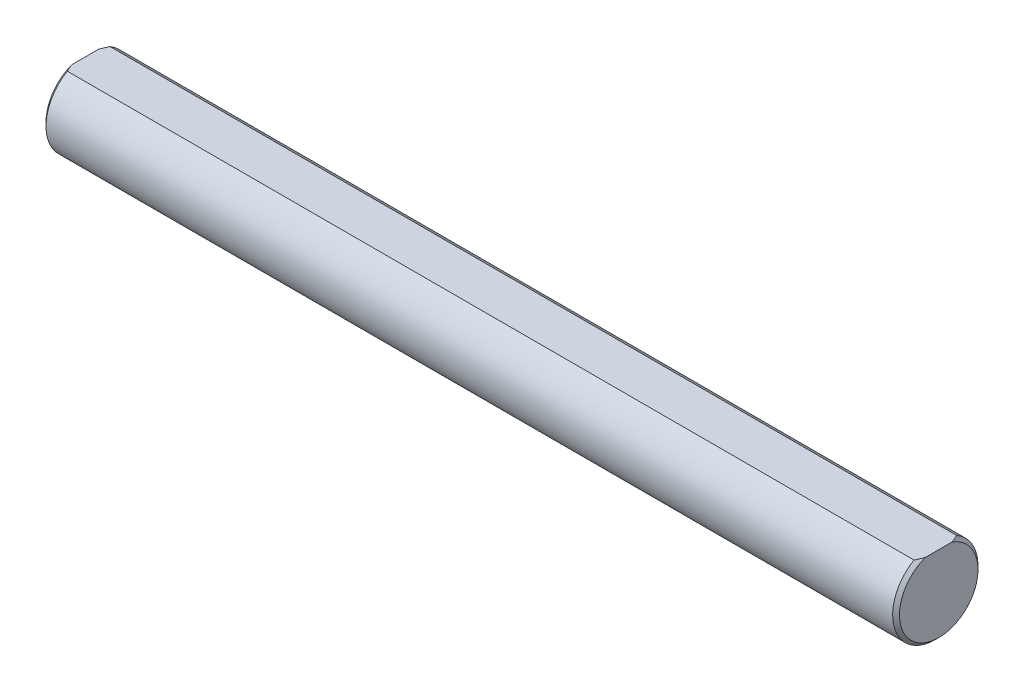
SolidWorks part; units mm, degrees
material "AISI 1045 Steel, cold drawn"
ref_plane "Front Plane" through (0, 0, 0) normal (0, 0, 1) x (1, 0, 0)
ref_plane "Top Plane" through (0, 0, 0) normal (0, 1, 0) x (1, 0, 0)
ref_plane "Right Plane" through (0, 0, 0) normal (1, 0, 0) x (0, 0, -1)
sketch "Sketch1" plane through (0, 0, 0) normal (1, 0, 0) x (0, 0, -1)
  circle A2 centre (0, 0) radius 3.175
  dimension "D1" = 6.35
extrude "Boss-Extrude1" add sketch "Sketch1" along normal blind 63.5
chamfer "Chamfer1" distance 0.254 angle 45 2 edges at (63.5, 0, -3.175) (0, 0, -3.175)
sketch "Sketch2" plane through (63.5, 0, 0) normal (1, 0, 0) x (0, 0, -1)
  line L0 (-1.5875, 2.7496) -> (1.5875, 2.7496)
  circle A0 centre (0, 0) radius 3.175 construction
  arc A1 (1.5875, 2.7496) -> (-1.5875, 2.7496) centre (0, 0) ccw
  dimension "D1" = 3.175
extrude "Cut-Extrude2" cut sketch "Sketch2" against normal through all
